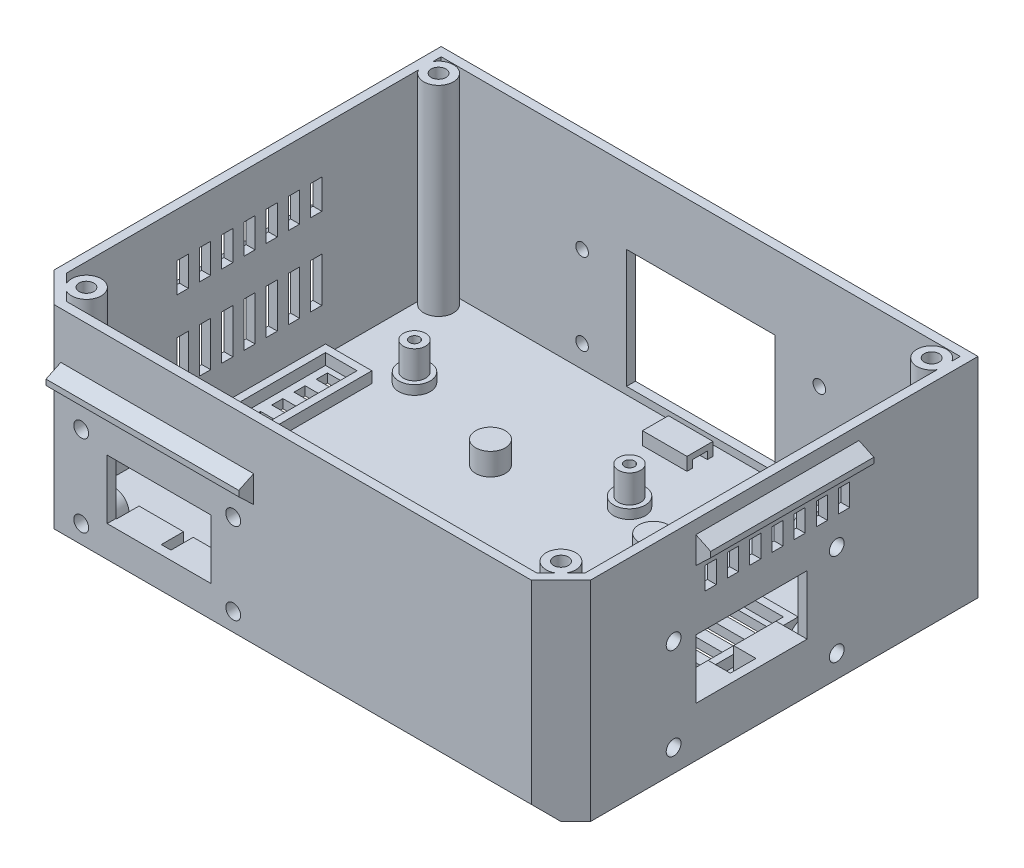
SolidWorks part; units mm, degrees
ref_plane "Front Plane" through (0, 0, 0) normal (0, 0, 1) x (1, 0, 0)
ref_plane "Top Plane" through (0, 0, 0) normal (0, 1, 0) x (1, 0, 0)
ref_plane "Right Plane" through (0, 0, 0) normal (1, 0, 0) x (0, 0, -1)
ref_plane "PZm28_4" through (0, -28.4, 0) normal (0, 1, 0) x (1, 0, 0)
sketch "Sketch1" plane through (0, -28.4, 0) normal (0, 1, 0) x (1, 0, 0)
  line L0 (-64.4, -124.4) -> (64.4, -124.4)
  line L1 (64.4, -124.4) -> (72.4, -116.4)
  line L2 (72.4, -116.4) -> (72.4, -11.9)
  line L3 (72.4, -11.9) -> (-72.4, -11.9)
  line L4 (-72.4, -11.9) -> (-72.4, -116.4)
  line L5 (-72.4, -116.4) -> (-64.4, -124.4)
extrude "Box Block" add sketch "Sketch1" along normal blind 56.4
sketch "Sketch2" plane through (0, 0, 0) normal (1, 0, 0) x (0, 0, -1)
  line L0 (-125.4, -23.4) -> (-119.4, -29.4)
  line L1 (-119.4, -29.4) -> (-125.4, -29.4)
  line L2 (-125.4, -29.4) -> (-125.4, -23.4)
extrude "Rear Bottom Facet" cut sketch "Sketch2" against normal through all and the other way through all
shell "Shell" thickness 2.4 removed face at (0, 28, 84.2333)
ref_plane "PY11_4" through (0, 0, 11.4) normal (0, 0, 1) x (1, 0, 0)
sketch "Sketch3" plane through (0, 0, 11.4) normal (0, 0, 1) x (1, 0, 0)
  line L0 (-20, -24) -> (20, -24)
  line L1 (20, -24) -> (20, 8)
  line L2 (20, 8) -> (-20, 8)
  line L3 (-20, 8) -> (-20, -24)
  circle A0 centre (-32, 2) radius 1.7
  circle A1 centre (32, 2) radius 1.7
  circle A2 centre (-32, -20) radius 1.7
  circle A3 centre (32, -20) radius 1.7
extrude "Cable Window and Flange Holes" cut sketch "Sketch3" along normal blind 3.4
ref_plane "PZm26_5" through (0, -26.5, 0) normal (0, 1, 0) x (1, 0, 0)
sketch "Sketch4" plane through (0, -26.5, 0) normal (0, 1, 0) x (1, 0, 0)
  circle A0 centre (-51.5, -89) radius 3
  circle A1 centre (6.5, -89) radius 3
  circle A2 centre (-51.5, -40) radius 3
  circle A3 centre (6.5, -40) radius 3
extrude "Pi Standoffs" add sketch "Sketch4" along normal blind 10.5
sketch "Sketch5" plane through (0, -26.5, 0) normal (0, 1, 0) x (1, 0, 0)
  circle A0 centre (-51.5, -89) radius 4.25
  circle A1 centre (6.5, -89) radius 4.25
  circle A2 centre (-51.5, -40) radius 4.25
  circle A3 centre (6.5, -40) radius 4.25
extrude "Pi Standoff Bases" add sketch "Sketch5" along normal blind 3
ref_plane "PZm28_9" through (0, -28.9, 0) normal (0, 1, 0) x (1, 0, 0)
sketch "Sketch6" plane through (0, -28.9, 0) normal (0, 1, 0) x (1, 0, 0)
  circle A0 centre (-51.5, -89) radius 1.35
  circle A1 centre (6.5, -89) radius 1.35
  circle A2 centre (-51.5, -40) radius 1.35
  circle A3 centre (6.5, -40) radius 1.35
extrude "Pi Screw Holes" cut sketch "Sketch6" along normal blind 13.4
sketch "Sketch7" plane through (0, -28.9, 0) normal (0, 1, 0) x (1, 0, 0)
  circle A0 centre (-51.5, -89) radius 2.75
  circle A1 centre (6.5, -89) radius 2.75
  circle A2 centre (-51.5, -40) radius 2.75
  circle A3 centre (6.5, -40) radius 2.75
extrude "Pi Counterbores" cut sketch "Sketch7" along normal blind 2.7
sketch "Sketch8" plane through (0, -26.5, 0) normal (0, 1, 0) x (1, 0, 0)
  circle A0 centre (-66.5, -18.5) radius 4
extrude "Lid Boss 1" add sketch "Sketch8" along normal blind 54.5
sketch "Sketch9" plane through (0, -26.5, 0) normal (0, 1, 0) x (1, 0, 0)
  circle A0 centre (66.5, -18.5) radius 4
extrude "Lid Boss 2" add sketch "Sketch9" along normal blind 54.5
sketch "Sketch10" plane through (0, -26.5, 0) normal (0, 1, 0) x (1, 0, 0)
  circle A0 centre (-64, -116) radius 4
extrude "Lid Boss 3" add sketch "Sketch10" along normal blind 54.5
sketch "Sketch11" plane through (0, -26.5, 0) normal (0, 1, 0) x (1, 0, 0)
  circle A0 centre (64, -116) radius 4
extrude "Lid Boss 4" add sketch "Sketch11" along normal blind 54.5
ref_plane "PZ22" through (0, 22, 0) normal (0, 1, 0) x (1, 0, 0)
sketch "Sketch12" plane through (0, 22, 0) normal (0, 1, 0) x (1, 0, 0)
  circle A0 centre (-66.5, -18.5) radius 2
  circle A1 centre (66.5, -18.5) radius 2
  circle A2 centre (-64, -116) radius 2
  circle A3 centre (64, -116) radius 2
extrude "Lid Insert Holes" cut sketch "Sketch12" along normal blind 6.5
sketch "Sketch13" plane through (0, -26.5, 0) normal (0, 1, 0) x (1, 0, 0)
  line L0 (38, -86) -> (58, -86)
  line L1 (58, -86) -> (58, -46)
  line L2 (58, -46) -> (38, -46)
  line L3 (38, -46) -> (38, -86)
  line L4 (40, -84) -> (56, -84)
  line L5 (56, -84) -> (56, -48)
  line L6 (56, -48) -> (40, -48)
  line L7 (40, -48) -> (40, -84)
extrude "Intake Upstand" add sketch "Sketch13" along normal blind 3.5
ref_plane "PZm29_4" through (0, -29.4, 0) normal (0, 1, 0) x (1, 0, 0)
sketch "Sketch14" plane through (0, -29.4, 0) normal (0, 1, 0) x (1, 0, 0)
  line L0 (42, -82.5) -> (54, -82.5)
  line L1 (54, -82.5) -> (54, -79.5)
  line L2 (54, -79.5) -> (42, -79.5)
  line L3 (42, -79.5) -> (42, -82.5)
  line L4 (42, -76.5) -> (54, -76.5)
  line L5 (54, -76.5) -> (54, -73.5)
  line L6 (54, -73.5) -> (42, -73.5)
  line L7 (42, -73.5) -> (42, -76.5)
  line L8 (42, -70.5) -> (54, -70.5)
  line L9 (54, -70.5) -> (54, -67.5)
  line L10 (54, -67.5) -> (42, -67.5)
  line L11 (42, -67.5) -> (42, -70.5)
  line L12 (42, -64.5) -> (54, -64.5)
  line L13 (54, -64.5) -> (54, -61.5)
  line L14 (54, -61.5) -> (42, -61.5)
  line L15 (42, -61.5) -> (42, -64.5)
  line L16 (42, -58.5) -> (54, -58.5)
  line L17 (54, -58.5) -> (54, -55.5)
  line L18 (54, -55.5) -> (42, -55.5)
  line L19 (42, -55.5) -> (42, -58.5)
  line L20 (42, -52.5) -> (54, -52.5)
  line L21 (54, -52.5) -> (54, -49.5)
  line L22 (54, -49.5) -> (42, -49.5)
  line L23 (42, -49.5) -> (42, -52.5)
extrude "Intake Slots" cut sketch "Sketch14" along normal blind 3.9
sketch "Sketch15" plane through (0, -26.5, 0) normal (0, 1, 0) x (1, 0, 0)
  line L0 (-69.5, -86) -> (-57, -86)
  line L1 (-57, -86) -> (-57, -46)
  line L2 (-57, -46) -> (-69.5, -46)
  line L3 (-69.5, -46) -> (-69.5, -86)
  line L4 (-67.5, -84) -> (-59, -84)
  line L5 (-59, -84) -> (-59, -48)
  line L6 (-59, -48) -> (-67.5, -48)
  line L7 (-67.5, -48) -> (-67.5, -84)
extrude "Floor Exhaust Upstand" add sketch "Sketch15" along normal blind 3.5
sketch "Sketch16" plane through (0, -29.4, 0) normal (0, 1, 0) x (1, 0, 0)
  line L0 (-65.5, -82.5) -> (-61, -82.5)
  line L1 (-61, -82.5) -> (-61, -79.5)
  line L2 (-61, -79.5) -> (-65.5, -79.5)
  line L3 (-65.5, -79.5) -> (-65.5, -82.5)
  line L4 (-65.5, -76.5) -> (-61, -76.5)
  line L5 (-61, -76.5) -> (-61, -73.5)
  line L6 (-61, -73.5) -> (-65.5, -73.5)
  line L7 (-65.5, -73.5) -> (-65.5, -76.5)
  line L8 (-65.5, -70.5) -> (-61, -70.5)
  line L9 (-61, -70.5) -> (-61, -67.5)
  line L10 (-61, -67.5) -> (-65.5, -67.5)
  line L11 (-65.5, -67.5) -> (-65.5, -70.5)
  line L12 (-65.5, -64.5) -> (-61, -64.5)
  line L13 (-61, -64.5) -> (-61, -61.5)
  line L14 (-61, -61.5) -> (-65.5, -61.5)
  line L15 (-65.5, -61.5) -> (-65.5, -64.5)
  line L16 (-65.5, -58.5) -> (-61, -58.5)
  line L17 (-61, -58.5) -> (-61, -55.5)
  line L18 (-61, -55.5) -> (-65.5, -55.5)
  line L19 (-65.5, -55.5) -> (-65.5, -58.5)
  line L20 (-65.5, -52.5) -> (-61, -52.5)
  line L21 (-61, -52.5) -> (-61, -49.5)
  line L22 (-61, -49.5) -> (-65.5, -49.5)
  line L23 (-65.5, -49.5) -> (-65.5, -52.5)
extrude "Floor Exhaust Slots" cut sketch "Sketch16" along normal blind 3.9
ref_plane "PXm72_9" through (-72.9, 0, 0) normal (1, 0, 0) x (0, 0, -1)
sketch "Sketch17" plane through (-72.9, 0, 0) normal (1, 0, 0) x (0, 0, -1)
  line L0 (-85.5, -14) -> (-82.5, -14)
  line L1 (-82.5, -14) -> (-82.5, -2)
  line L2 (-82.5, -2) -> (-85.5, -2)
  line L3 (-85.5, -2) -> (-85.5, -14)
  line L4 (-79.5, -14) -> (-76.5, -14)
  line L5 (-76.5, -14) -> (-76.5, -2)
  line L6 (-76.5, -2) -> (-79.5, -2)
  line L7 (-79.5, -2) -> (-79.5, -14)
  line L8 (-73.5, -14) -> (-70.5, -14)
  line L9 (-70.5, -14) -> (-70.5, -2)
  line L10 (-70.5, -2) -> (-73.5, -2)
  line L11 (-73.5, -2) -> (-73.5, -14)
  line L12 (-67.5, -14) -> (-64.5, -14)
  line L13 (-64.5, -14) -> (-64.5, -2)
  line L14 (-64.5, -2) -> (-67.5, -2)
  line L15 (-67.5, -2) -> (-67.5, -14)
  line L16 (-61.5, -14) -> (-58.5, -14)
  line L17 (-58.5, -14) -> (-58.5, -2)
  line L18 (-58.5, -2) -> (-61.5, -2)
  line L19 (-61.5, -2) -> (-61.5, -14)
  line L20 (-55.5, -14) -> (-52.5, -14)
  line L21 (-52.5, -14) -> (-52.5, -2)
  line L22 (-52.5, -2) -> (-55.5, -2)
  line L23 (-55.5, -2) -> (-55.5, -14)
  line L24 (-49.5, -14) -> (-46.5, -14)
  line L25 (-46.5, -14) -> (-46.5, -2)
  line L26 (-46.5, -2) -> (-49.5, -2)
  line L27 (-49.5, -2) -> (-49.5, -14)
extrude "Exhaust Vents" cut sketch "Sketch17" along normal blind 3.4
ref_plane "PY44" through (0, 0, 44) normal (0, 0, 1) x (1, 0, 0)
sketch "Sketch18" plane through (0, 0, 44) normal (0, 0, 1) x (1, 0, 0)
  line L0 (-72.2, -0.5) -> (-76.4, 3.5)
  line L1 (-76.4, 3.5) -> (-76.4, 5)
  line L2 (-76.4, 5) -> (-72.2, 7)
  line L3 (-72.2, 7) -> (-72.2, -0.5)
extrude "Exhaust Drip Ledge" add sketch "Sketch18" along normal blind 44
sketch "Sketch19" plane through (-72.9, 0, 0) normal (1, 0, 0) x (0, 0, -1)
  line L0 (-85.5, 8) -> (-82.5, 8)
  line L1 (-82.5, 8) -> (-82.5, 16)
  line L2 (-82.5, 16) -> (-85.5, 16)
  line L3 (-85.5, 16) -> (-85.5, 8)
  line L4 (-79.5, 8) -> (-76.5, 8)
  line L5 (-76.5, 8) -> (-76.5, 16)
  line L6 (-76.5, 16) -> (-79.5, 16)
  line L7 (-79.5, 16) -> (-79.5, 8)
  line L8 (-73.5, 8) -> (-70.5, 8)
  line L9 (-70.5, 8) -> (-70.5, 16)
  line L10 (-70.5, 16) -> (-73.5, 16)
  line L11 (-73.5, 16) -> (-73.5, 8)
  line L12 (-67.5, 8) -> (-64.5, 8)
  line L13 (-64.5, 8) -> (-64.5, 16)
  line L14 (-64.5, 16) -> (-67.5, 16)
  line L15 (-67.5, 16) -> (-67.5, 8)
  line L16 (-61.5, 8) -> (-58.5, 8)
  line L17 (-58.5, 8) -> (-58.5, 16)
  line L18 (-58.5, 16) -> (-61.5, 16)
  line L19 (-61.5, 16) -> (-61.5, 8)
  line L20 (-55.5, 8) -> (-52.5, 8)
  line L21 (-52.5, 8) -> (-52.5, 16)
  line L22 (-52.5, 16) -> (-55.5, 16)
  line L23 (-55.5, 16) -> (-55.5, 8)
  line L24 (-49.5, 8) -> (-46.5, 8)
  line L25 (-46.5, 8) -> (-46.5, 16)
  line L26 (-46.5, 16) -> (-49.5, 16)
  line L27 (-49.5, 16) -> (-49.5, 8)
extrude "Upper Vents L" cut sketch "Sketch19" along normal blind 3.4
sketch "Sketch20" plane through (0, 0, 44) normal (0, 0, 1) x (1, 0, 0)
  line L0 (-72.2, 17) -> (-76.4, 21)
  line L1 (-76.4, 21) -> (-76.4, 22.5)
  line L2 (-76.4, 22.5) -> (-72.2, 24.5)
  line L3 (-72.2, 24.5) -> (-72.2, 17)
extrude "Upper Drip Ledge L" add sketch "Sketch20" along normal blind 44
ref_plane "PX69_5" through (69.5, 0, 0) normal (1, 0, 0) x (0, 0, -1)
sketch "Sketch21" plane through (69.5, 0, 0) normal (1, 0, 0) x (0, 0, -1)
  line L0 (-85.5, 10) -> (-82.5, 10)
  line L1 (-82.5, 10) -> (-82.5, 16)
  line L2 (-82.5, 16) -> (-85.5, 16)
  line L3 (-85.5, 16) -> (-85.5, 10)
  line L4 (-79.5, 10) -> (-76.5, 10)
  line L5 (-76.5, 10) -> (-76.5, 16)
  line L6 (-76.5, 16) -> (-79.5, 16)
  line L7 (-79.5, 16) -> (-79.5, 10)
  line L8 (-73.5, 10) -> (-70.5, 10)
  line L9 (-70.5, 10) -> (-70.5, 16)
  line L10 (-70.5, 16) -> (-73.5, 16)
  line L11 (-73.5, 16) -> (-73.5, 10)
  line L12 (-67.5, 10) -> (-64.5, 10)
  line L13 (-64.5, 10) -> (-64.5, 16)
  line L14 (-64.5, 16) -> (-67.5, 16)
  line L15 (-67.5, 16) -> (-67.5, 10)
  line L16 (-61.5, 10) -> (-58.5, 10)
  line L17 (-58.5, 10) -> (-58.5, 16)
  line L18 (-58.5, 16) -> (-61.5, 16)
  line L19 (-61.5, 16) -> (-61.5, 10)
  line L20 (-55.5, 10) -> (-52.5, 10)
  line L21 (-52.5, 10) -> (-52.5, 16)
  line L22 (-52.5, 16) -> (-55.5, 16)
  line L23 (-55.5, 16) -> (-55.5, 10)
  line L24 (-49.5, 10) -> (-46.5, 10)
  line L25 (-46.5, 10) -> (-46.5, 16)
  line L26 (-46.5, 16) -> (-49.5, 16)
  line L27 (-49.5, 16) -> (-49.5, 10)
extrude "Upper Vents R" cut sketch "Sketch21" along normal blind 3.4
sketch "Sketch22" plane through (0, 0, 44) normal (0, 0, 1) x (1, 0, 0)
  line L0 (72.2, 17) -> (76.4, 21)
  line L1 (76.4, 21) -> (76.4, 22.5)
  line L2 (76.4, 22.5) -> (72.2, 24.5)
  line L3 (72.2, 24.5) -> (72.2, 17)
extrude "Upper Drip Ledge R" add sketch "Sketch22" along normal blind 44
ref_plane "PY121_5" through (0, 0, 121.5) normal (0, 0, 1) x (1, 0, 0)
sketch "Sketch23" plane through (0, 0, 121.5) normal (0, 0, 1) x (1, 0, 0)
  line L0 (-50, -16) -> (-22, -16)
  line L1 (-22, -16) -> (-22, 0)
  line L2 (-22, 0) -> (-50, 0)
  line L3 (-50, 0) -> (-50, -16)
extrude "Rear Port Opening" cut sketch "Sketch23" along normal blind 3.4
ref_plane "PY115_5" through (0, 0, 115.5) normal (0, 0, 1) x (1, 0, 0)
sketch "Sketch24" plane through (0, 0, 115.5) normal (0, 0, 1) x (1, 0, 0)
  circle A0 centre (-57, -19.5) radius 4
  circle A1 centre (-57, 2.5) radius 4
  circle A2 centre (-16, -19.5) radius 4
  circle A3 centre (-16, 2.5) radius 4
extrude "Rear Port Bosses" add sketch "Sketch24" along normal blind 6.6
sketch "Sketch25" plane through (0, 0, 115.5) normal (0, 0, 1) x (1, 0, 0)
  line L0 (-61, -26.5) -> (-53, -26.5)
  line L1 (-53, -26.5) -> (-53, -19.5)
  line L2 (-53, -19.5) -> (-61, -19.5)
  line L3 (-61, -19.5) -> (-61, -26.5)
  line L4 (-20, -26.5) -> (-12, -26.5)
  line L5 (-12, -26.5) -> (-12, -19.5)
  line L6 (-12, -19.5) -> (-20, -19.5)
  line L7 (-20, -19.5) -> (-20, -26.5)
extrude "Rear Port Boss Roots" add sketch "Sketch25" along normal blind 6.6
ref_plane "PXm61" through (-61, 0, 0) normal (1, 0, 0) x (0, 0, -1)
sketch "Sketch26" plane through (-61, 0, 0) normal (1, 0, 0) x (0, 0, -1)
  line L0 (-122.1, 2.5) -> (-115.5, 2.5)
  line L1 (-115.5, 2.5) -> (-115.5, -1.5)
  line L2 (-115.5, -1.5) -> (-122.1, -8.1)
  line L3 (-122.1, -8.1) -> (-122.1, 2.5)
extrude "Rear Boss Gusset -57" add sketch "Sketch26" along normal blind 8
ref_plane "PXm20" through (-20, 0, 0) normal (1, 0, 0) x (0, 0, -1)
sketch "Sketch27" plane through (-20, 0, 0) normal (1, 0, 0) x (0, 0, -1)
  line L0 (-122.1, 2.5) -> (-115.5, 2.5)
  line L1 (-115.5, 2.5) -> (-115.5, -1.5)
  line L2 (-115.5, -1.5) -> (-122.1, -8.1)
  line L3 (-122.1, -8.1) -> (-122.1, 2.5)
extrude "Rear Boss Gusset -16" add sketch "Sketch27" along normal blind 8
ref_plane "PY117_9" through (0, 0, 117.9) normal (0, 0, 1) x (1, 0, 0)
sketch "Sketch28" plane through (0, 0, 117.9) normal (0, 0, 1) x (1, 0, 0)
  circle A0 centre (-57, -19.5) radius 2
  circle A1 centre (-57, 2.5) radius 2
  circle A2 centre (-16, -19.5) radius 2
  circle A3 centre (-16, 2.5) radius 2
extrude "Rear Port Insert Holes" cut sketch "Sketch28" along normal blind 7
ref_plane "PXm62_5" through (-62.5, 0, 0) normal (1, 0, 0) x (0, 0, -1)
sketch "Sketch29" plane through (-62.5, 0, 0) normal (1, 0, 0) x (0, 0, -1)
  line L0 (-124.2, 8) -> (-128.4, 12)
  line L1 (-128.4, 12) -> (-128.4, 13.5)
  line L2 (-128.4, 13.5) -> (-124.2, 15.5)
  line L3 (-124.2, 15.5) -> (-124.2, 8)
extrude "Rear Port Drip Ledge" add sketch "Sketch29" along normal blind 52
sketch "Sketch30" plane through (0, -26.5, 0) normal (0, 1, 0) x (1, 0, 0)
  line L0 (-49.8, -122.1) -> (-37.8, -122.1)
  line L1 (-37.8, -122.1) -> (-37.8, -116)
  line L2 (-37.8, -116) -> (-49.8, -116)
  line L3 (-49.8, -116) -> (-49.8, -122.1)
extrude "Rear Tie Block usbc" add sketch "Sketch30" along normal blind 10.5
ref_plane "PXm50_8" through (-50.8, 0, 0) normal (1, 0, 0) x (0, 0, -1)
sketch "Sketch31" plane through (-50.8, 0, 0) normal (1, 0, 0) x (0, 0, -1)
  line L0 (-120.5, -24.5) -> (-117.5, -24.5)
  line L1 (-117.5, -24.5) -> (-117.5, -22.5)
  line L2 (-117.5, -22.5) -> (-120.5, -22.5)
  line L3 (-120.5, -22.5) -> (-120.5, -24.5)
extrude "Rear Tie Tunnel usbc" cut sketch "Sketch31" along normal blind 14
sketch "Sketch32" plane through (0, -26.5, 0) normal (0, 1, 0) x (1, 0, 0)
  line L0 (-35.2, -122.1) -> (-23.2, -122.1)
  line L1 (-23.2, -122.1) -> (-23.2, -116)
  line L2 (-23.2, -116) -> (-35.2, -116)
  line L3 (-35.2, -116) -> (-35.2, -122.1)
extrude "Rear Tie Block hdmi" add sketch "Sketch32" along normal blind 10.5
ref_plane "PXm36_2" through (-36.2, 0, 0) normal (1, 0, 0) x (0, 0, -1)
sketch "Sketch33" plane through (-36.2, 0, 0) normal (1, 0, 0) x (0, 0, -1)
  line L0 (-120.5, -24.5) -> (-117.5, -24.5)
  line L1 (-117.5, -24.5) -> (-117.5, -22.5)
  line L2 (-117.5, -22.5) -> (-120.5, -22.5)
  line L3 (-120.5, -22.5) -> (-120.5, -24.5)
extrude "Rear Tie Tunnel hdmi" cut sketch "Sketch33" along normal blind 14
sketch "Sketch34" plane through (69.5, 0, 0) normal (1, 0, 0) x (0, 0, -1)
  line L0 (-88, -15) -> (-58, -15)
  line L1 (-58, -15) -> (-58, 1)
  line L2 (-58, 1) -> (-88, 1)
  line L3 (-88, 1) -> (-88, -15)
extrude "Side Port Opening" cut sketch "Sketch34" along normal blind 3.4
ref_plane "PX63_5" through (63.5, 0, 0) normal (1, 0, 0) x (0, 0, -1)
sketch "Sketch35" plane through (63.5, 0, 0) normal (1, 0, 0) x (0, 0, -1)
  circle A0 centre (-94, -22.3) radius 4
  circle A1 centre (-94, 2.5) radius 4
  circle A2 centre (-50, -22.3) radius 4
  circle A3 centre (-50, 2.5) radius 4
extrude "Side Port Bosses" add sketch "Sketch35" along normal blind 6.6
ref_plane "PY90" through (0, 0, 90) normal (0, 0, 1) x (1, 0, 0)
sketch "Sketch36" plane through (0, 0, 90) normal (0, 0, 1) x (1, 0, 0)
  line L0 (70.1, 2.5) -> (63.5, 2.5)
  line L1 (63.5, 2.5) -> (63.5, -1.5)
  line L2 (63.5, -1.5) -> (70.1, -8.1)
  line L3 (70.1, -8.1) -> (70.1, 2.5)
extrude "Side Boss Gusset -94" add sketch "Sketch36" along normal blind 8
ref_plane "PY46" through (0, 0, 46) normal (0, 0, 1) x (1, 0, 0)
sketch "Sketch37" plane through (0, 0, 46) normal (0, 0, 1) x (1, 0, 0)
  line L0 (70.1, 2.5) -> (63.5, 2.5)
  line L1 (63.5, 2.5) -> (63.5, -1.5)
  line L2 (63.5, -1.5) -> (70.1, -8.1)
  line L3 (70.1, -8.1) -> (70.1, 2.5)
extrude "Side Boss Gusset -50" add sketch "Sketch37" along normal blind 8
ref_plane "PX65_9" through (65.9, 0, 0) normal (1, 0, 0) x (0, 0, -1)
sketch "Sketch38" plane through (65.9, 0, 0) normal (1, 0, 0) x (0, 0, -1)
  circle A0 centre (-94, -22.3) radius 2
  circle A1 centre (-94, 2.5) radius 2
  circle A2 centre (-50, -22.3) radius 2
  circle A3 centre (-50, 2.5) radius 2
extrude "Side Port Insert Holes" cut sketch "Sketch38" along normal blind 7
sketch "Sketch39" plane through (0, -26.5, 0) normal (0, 1, 0) x (1, 0, 0)
  line L0 (64, -88) -> (70.1, -88)
  line L1 (70.1, -88) -> (70.1, -76.3)
  line L2 (70.1, -76.3) -> (64, -76.3)
  line L3 (64, -76.3) -> (64, -88)
extrude "Side Tie Block eth" add sketch "Sketch39" along normal blind 11.5
ref_plane "PY75_3" through (0, 0, 75.3) normal (0, 0, 1) x (1, 0, 0)
sketch "Sketch40" plane through (0, 0, 75.3) normal (0, 0, 1) x (1, 0, 0)
  line L0 (65.5, -24.5) -> (68.5, -24.5)
  line L1 (68.5, -24.5) -> (68.5, -22.5)
  line L2 (68.5, -22.5) -> (65.5, -22.5)
  line L3 (65.5, -22.5) -> (65.5, -24.5)
extrude "Side Tie Tunnel eth" cut sketch "Sketch40" along normal blind 14
sketch "Sketch41" plane through (0, -26.5, 0) normal (0, 1, 0) x (1, 0, 0)
  line L0 (64, -69.4) -> (70.1, -69.4)
  line L1 (70.1, -69.4) -> (70.1, -58)
  line L2 (70.1, -58) -> (64, -58)
  line L3 (64, -58) -> (64, -69.4)
extrude "Side Tie Block usba" add sketch "Sketch41" along normal blind 11.5
ref_plane "PY56_4" through (0, 0, 56.4) normal (0, 0, 1) x (1, 0, 0)
sketch "Sketch42" plane through (0, 0, 56.4) normal (0, 0, 1) x (1, 0, 0)
  line L0 (65.5, -24.5) -> (68.5, -24.5)
  line L1 (68.5, -24.5) -> (68.5, -22.5)
  line L2 (68.5, -22.5) -> (65.5, -22.5)
  line L3 (65.5, -22.5) -> (65.5, -24.5)
extrude "Side Tie Tunnel usba" cut sketch "Sketch42" along normal blind 14
sketch "Sketch43" plane through (0, -26.5, 0) normal (0, 1, 0) x (1, 0, 0)
  line L0 (-6, -24) -> (6, -24)
  line L1 (6, -24) -> (6, -17)
  line L2 (6, -17) -> (-6, -17)
  line L3 (-6, -17) -> (-6, -24)
extrude "Bundle Tie Anchor" add sketch "Sketch43" along normal blind 4
ref_plane "PXm7" through (-7, 0, 0) normal (1, 0, 0) x (0, 0, -1)
sketch "Sketch44" plane through (-7, 0, 0) normal (1, 0, 0) x (0, 0, -1)
  line L0 (-22.5, -26) -> (-18.5, -26)
  line L1 (-18.5, -26) -> (-18.5, -24)
  line L2 (-18.5, -24) -> (-22.5, -24)
  line L3 (-22.5, -24) -> (-22.5, -26)
extrude "Bundle Tie Slot" cut sketch "Sketch44" along normal blind 14
sketch "Sketch45" plane through (0, -26.5, 0) normal (0, 1, 0) x (1, 0, 0)
  circle A0 centre (-22, -91) radius 4
  circle A1 centre (-22, -49) radius 4
  circle A2 centre (22, -91) radius 4
  circle A3 centre (22, -49) radius 4
extrude "Rail Plate Bosses" add sketch "Sketch45" along normal blind 6.5
sketch "Sketch46" plane through (0, -28.9, 0) normal (0, 1, 0) x (1, 0, 0)
  circle A0 centre (-22, -91) radius 2
  circle A1 centre (-22, -49) radius 2
  circle A2 centre (22, -91) radius 2
  circle A3 centre (22, -49) radius 2
extrude "Rail Insert Holes" cut sketch "Sketch46" along normal blind 6.5
equation "\"BOARD_REAR\" = 86.0"
equation "\"BOARD_FRONT\" = 41.0"
equation "\"BOARD_END\" = 22.0"
equation "\"BOARD_ANGLED\" = 30.0"
equation "\"BOARD_DEPTH\" = 41.8431"
equation "\"PCB_T\" = 1.6"
equation "\"ABOVE_PCB\" = 14.0"
equation "\"BELOW_PCB\" = 6.0"
equation "\"MID_PARTS_H\" = 9.0"
equation "\"BOARD_HOLE_PILOT\" = 1.6"
equation "\"J2_X\" = 19.0"
equation "\"DUPONT_DROP\" = 14.0"
equation "\"BEND_R\" = 5.0"
equation "\"BOARD_GAP\" = 3.0"
equation "\"TOF_FOV\" = 25.0"
equation "\"TOF_MARGIN_DEG\" = 5.0"
equation "\"TOF_WIN_MARGIN\" = 1.0"
equation "\"TOF_Z\" = 9.0"
equation "\"TOF_SIDE_BEARING\" = 90.0"
equation "\"TOF_CONE_LEN\" = 70.0"
equation "\"CAM_W\" = 29.2"
equation "\"CAM_H\" = 28.2"
equation "\"CAM_D\" = 12.35"
equation "\"CAM_FRONT_Y\" = 43.0"
equation "\"CAM_BOTTOM_Z\" = 17.0"
equation "\"CAM_LENS_UP\" = 11.6"
equation "\"CAM_LENS_OPEN\" = 9.6"
equation "\"CAM_HFOV\" = 53.5"
equation "\"CAM_VFOV\" = 41.41"
equation "\"CAM_FOV_MARGIN\" = 3.0"
equation "\"CAM_FIT\" = 0.3"
equation "\"RIBBON_W\" = 16.0"
equation "\"RIBBON_T\" = 0.3"
equation "\"RIBBON_LEN\" = 150.0"
equation "\"RIBBON_EXIT_Y\" = 35.0"
equation "\"WALL\" = 2.4"
equation "\"HEAD_X\" = 48.4"
equation "\"HEAD_REAR_Y\" = -11.9"
equation "\"CAM_FOAM\" = 2.8"
equation "\"HEAD_FRONT_Y\" = 48.2"
equation "\"HEAD_TOP_Z\" = 50.6"
equation "\"HEAD_BOT_Z\" = -28.4"
equation "\"HEAD_SPLIT_Z\" = -4.0"
equation "\"SKIRT_T\" = 1.2"
equation "\"SKIRT_H\" = 3.0"
equation "\"SKIRT_FIT\" = 0.3"
equation "\"VISOR\" = 7.8"
equation "\"VISOR_Z\" = 40.0"
equation "\"ROOF_SLOPE_Y\" = 40.0"
equation "\"ROOF_CHAMFER\" = 10.0"
equation "\"REAR_CHAMFER\" = 10.0"
equation "\"CORNER_CHAMFER\" = 6.0"
equation "\"LOWER_SIDE_FACET\" = 6.0"
equation "\"LIGHTBAR_DEPTH\" = 1.0"
equation "\"HOOD_Z\" = 14.0"
equation "\"HOOD_L\" = 6.0"
equation "\"SIDE_HOOD_L\" = 4.0"
equation "\"INSERT_M3_D\" = 4.0"
equation "\"INSERT_M3_L\" = 6.0"
equation "\"M3_CLEAR\" = 3.4"
equation "\"M2_PILOT\" = 1.6"
equation "\"M25_PILOT\" = 2.2"
equation "\"BOX_X\" = 72.4"
equation "\"BOX_FRONT_Y\" = -11.9"
equation "\"BOX_REAR_Y\" = -124.4"
equation "\"BOX_BOT_Z\" = -28.4"
equation "\"BOX_TOP_Z\" = 28.0"
equation "\"LID_T\" = 2.4"
equation "\"LID_SKIRT\" = 1.6"
equation "\"LID_TONGUE_H\" = 3.0"
equation "\"LID_FIT\" = 0.3"
equation "\"PI_STANDOFF\" = 10.0"
equation "\"BOX_REAR_CHAMFER\" = 8.0"
equation "\"BOX_REAR_FACET\" = 4.0"
equation "\"VENT_UPSTAND\" = 3.0"
equation "\"TUBE_D\" = 22.2"
equation "\"TUBE_LINER\" = 1.0"
equation "\"MOUNT_Y\" = -70.0"
equation "\"RAIL_W\" = 30.0"
equation "\"RAIL_W2\" = 38.0"
equation "\"RAIL_H\" = 6.0"
equation "\"SLIDE\" = 0.3"
equation "\"STOP_T\" = 6.0"
equation "\"CLAMP_W\" = 40.0"
equation "\"CLAMP_HALF\" = 20.0"
equation "\"CLAMP_DROP\" = 12.0"
equation "\"CAP_T\" = 12.0"
equation "\"CLAMP_BOLT_OFF\" = 16.6"
equation "\"M5_INSERT_D\" = 6.4"
equation "\"M5_CLEAR\" = 5.5"
equation "\"LOCK_D\" = 3.3"
equation "\"POD_TILT_DEG\" = 0.0"
equation "\"PRINT_LIMIT\" = 180.0"
equation "\"PI5_L\" = 85.0"
equation "\"PI5_W\" = 56.0"
equation "\"PI5_T\" = 1.6"
equation "\"PI5_USBC_BX\" = 11.2"
equation "\"PI5_ETH_BY\" = 10.2"
equation "\"PI5_PORT_OVERHANG\" = 3.0"
equation "\"PI5_FPC_H\" = 5.0"
equation "\"PI5_FPC_USE\" = 0.0"
equation "\"PI5_PIN1_BX\" = 8.37"
equation "\"HEADER_BASE_H\" = 2.5"
equation "\"DUPONT_L\" = 14.0"
equation "\"PI5_UNDERSIDE\" = 1.5"
equation "\"COOLER_H\" = 15.0"
equation "\"HAT_W\" = 65.0"
equation "\"HAT_D\" = 56.5"
equation "\"HAT_T\" = 1.6"
equation "\"HAT_SPACER\" = 16.0"
equation "\"HAILO_H\" = 10.0"
equation "\"STACK_PINS_H\" = 6.0"
equation "\"DUPONT_SEAT\" = 0.5"
equation "\"PCIE_FFC_LOOP\" = 6.0"
equation "\"HAILO_AIR_GAP_MIN\" = 8.0"
equation "\"M25_CLEAR\" = 2.7"
equation "\"PI_X0\" = -55.0"
equation "\"PI_Y1\" = -36.5"
equation "\"PI_Y0\" = -92.5"
equation "\"BOX_LEN\" = 112.5"
equation "\"COVER_T\" = 3.0"
equation "\"COVER_TOP_Z\" = 6.5"
equation "\"SIDE_LEDGE_Z\" = -0.5"
equation "\"UPPER_LEDGE_Z\" = 17.0"
equation "\"REAR_LEDGE_Z\" = 8.0"
equation "\"LEDGE_L\" = 4.0"
equation "\"LEDGE_TIP\" = 1.5"
equation "\"RIBBON_W_PI\" = 11.5"
equation "\"RIBBON_RUN_Z\" = 12.0"
equation "\"RIBBON_SPEC_LEN\" = 200.0"
